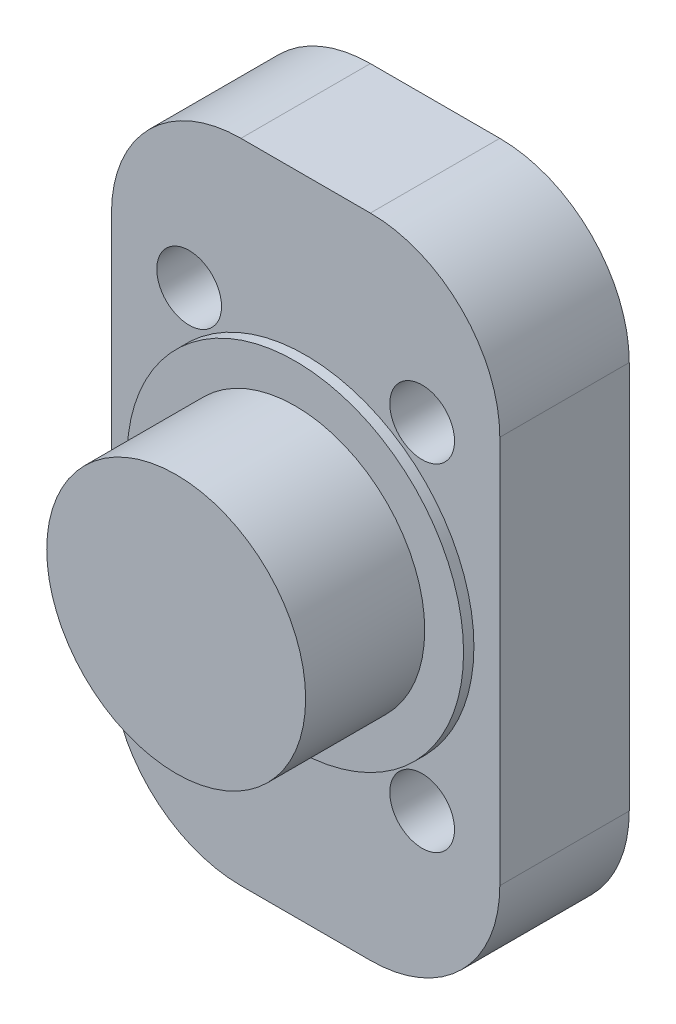
SolidWorks part; units mm, degrees
material "3.1325 (EN-AW 2017A)"
ref_plane "正面" through (0, 0, 0) normal (0, 0, 1) x (1, 0, 0)
ref_plane "平面" through (0, 0, 0) normal (0, 1, 0) x (1, 0, 0)
ref_plane "右側面" through (0, 0, 0) normal (1, 0, 0) x (0, 0, -1)
sketch "ｽｹｯﾁ1" plane through (0, 0, 0) normal (0, 0, 1) x (1, 0, 0)
  line L0 (0, 0) -> (0, 12.5) construction
  line L1 (-7.5, 12.5) -> (7.5, 12.5)
  line L2 (-7.5, 12.5) -> (-7.5, -12.5)
  line L3 (-7.5, -12.5) -> (7.5, -12.5)
  line L4 (7.5, 12.5) -> (7.5, -12.5)
  line L5 (-7.5, 12.5) -> (7.5, -12.5) construction
  line L6 (-7.5, -12.5) -> (7.5, 12.5) construction
  line L7 (0, 0) -> (7.5, 0) construction
  circle A0 centre (0, 0) radius 6.5
  circle A1 centre (0, 0) radius 5
  point P0 (0, 0)
  point P9 (-4.5, 6.5)
  point P10 (-4.5, -6.5)
  point P11 (4.5, -6.5)
  point P12 (4.5, 6.5)
  dimension "D3" = 13
  dimension "D4" = 10
  dimension "D1" = 15
  dimension "D2" = 25
  dimension "D5" = 13
  dimension "D6" = 9
extrude "ﾎﾞｽ - 押し出し1" add sketch "ｽｹｯﾁ1" against normal blind 5 contours L1 L4 L3 L2
extrude "ﾎﾞｽ - 押し出し2" add sketch "ｽｹｯﾁ1<3>" along normal blind 0.4 contours A0
sketch "ｽｹｯﾁ1<3>" plane through (0, 0, 0) normal (0, 0, 1) x (1, 0, 0) same geometry as "ｽｹｯﾁ1"
extrude "ﾎﾞｽ - 押し出し3" add sketch "ｽｹｯﾁ1<4>" along normal blind 5 contours A1
sketch "ｽｹｯﾁ1<4>" plane through (0, 0, 0) normal (0, 0, 1) x (1, 0, 0) same geometry as "ｽｹｯﾁ1"
hole_wizard "M3x0.5 ねじ穴用ねじ下穴ﾄﾞﾘﾙ1" positions "3Dｽｹｯﾁ1" profile "ｽｹｯﾁ2" hole size "M3x0.5" standard "JIS" end condition through all
sketch3d "3Dｽｹｯﾁ1"
  point P0 (-4.5, 6.5, 0)
  point P2 (4.5, 6.5, 0)
  point P4 (4.5, -6.5, 0)
  point P6 (-4.5, -6.5, 0)
sketch "ｽｹｯﾁ2" plane through (-4.5, 6.5, 0) normal (1, 0, 0) x (0, -1, 0)
  line L0 (0, 0) -> (0, 5)
  line L1 (0, 5) -> (1.25, 5)
  line L2 (1.25, 5) -> (1.25, 0)
  line L5 (1.25, 0) -> (0, 0)
  line L11 (0, -6.35) -> (0, 107.95) construction
  dimension "通し穴の直径" = 2.5
  dimension "通し穴の深さ" = 5
fillet "ﾌｨﾚｯﾄ1" radius 5 4 edges at (-7.5, -12.5, -2.5) (7.5, -12.5, -2.5) (7.5, 12.5, -2.5) (-7.5, 12.5, -2.5)
equation "\"ミル径\"= 1"
equation "\"コーナR面取り\"= 5"
equation "\"D1@ﾌｨﾚｯﾄ1\"=\"コーナR面取り\""
